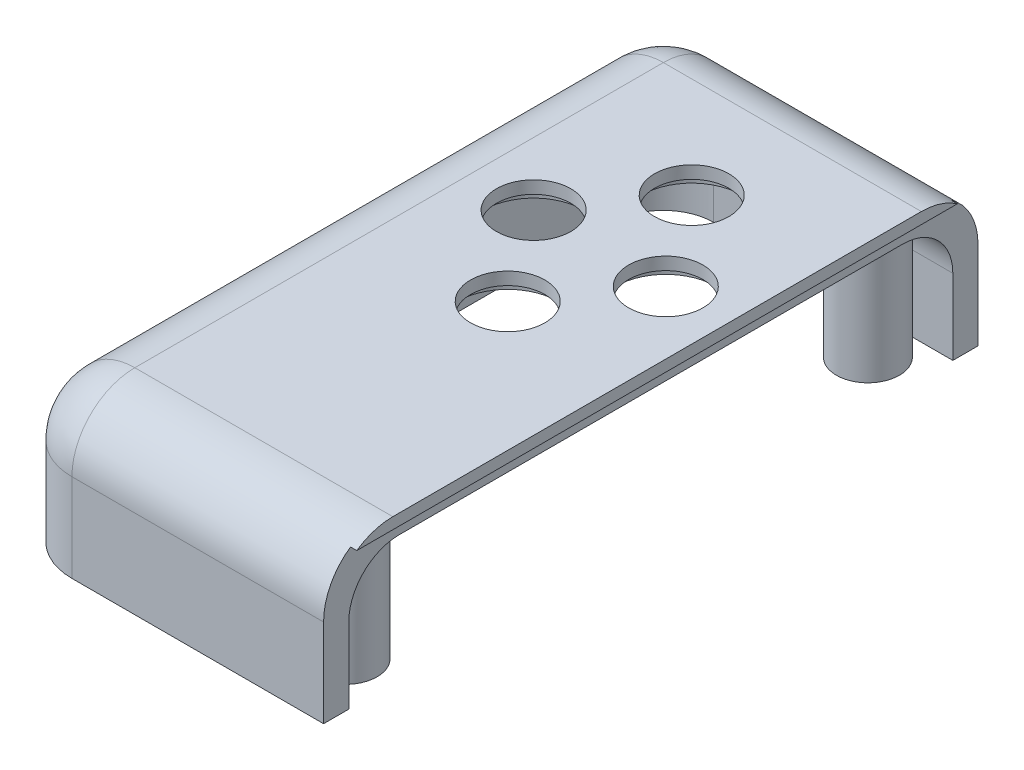
SolidWorks part; units mm, degrees
material "ABS"
ref_plane "Front Plane" through (0, 0, 0) normal (0, 0, 1) x (1, 0, 0)
ref_plane "Top Plane" through (0, 0, 0) normal (0, 1, 0) x (1, 0, 0)
ref_plane "Right Plane" through (0, 0, 0) normal (1, 0, 0) x (0, 0, -1)
sketch "Sketch1" plane through (0, 0, 0) normal (0, 1, 0) x (1, 0, 0)
  line L1 (0, 0) -> (63.5, 0)
  line L2 (0, 0) -> (0, 132.08)
  line L3 (0, 132.08) -> (63.5, 132.08)
  line L4 (63.5, 0) -> (63.5, 132.08)
  dimension "D1" = 132.08
  dimension "D2" = 63.5
extrude "Boss-Extrude1" add sketch "Sketch1" along normal blind 5.08
sketch "Sketch2" plane through (0, 0, 0) normal (0, -1, 0) x (1, 0, 0)
  line L0 (0, -132.08) -> (0, 0) construction
  line L1 (63.5, -132.08) -> (0, -132.08) construction
  circle A0 centre (54.356, -118.999) radius 6.35
  circle A1 centre (54.356, -118.999) radius 5.08
  circle A2 centre (54.356, -13.589) radius 6.35
  circle A3 centre (54.356, -13.589) radius 5.08
  dimension "D1" = 12.7
  dimension "D2" = 10.16
  dimension "D3" = 12.7
  dimension "D4" = 10.16
  dimension "D5" = 54.356
  dimension "D6" = 105.41
  dimension "D7" = 13.081
extrude "Boss-Extrude2" add sketch "Sketch2" along normal blind 25.4
sketch "Sketch3" plane through (0, 0, 0) normal (0, -1, 0) x (1, 0, 0)
  line L0 (63.5, -132.08) -> (0, -132.08)
  line L1 (0, -132.08) -> (0, 0)
  line L2 (0, 0) -> (63.5, 0)
  line L3 (63.5, 0) -> (63.5, -5.08)
  line L4 (63.5, 0) -> (63.5, -132.08) construction
  line L5 (63.5, -5.08) -> (5.08, -5.08)
  line L6 (5.08, -5.08) -> (5.08, -127)
  line L7 (5.08, -127) -> (63.5, -127)
  line L8 (63.5, -127) -> (63.5, -132.08)
  dimension "D1" = 5.08
  dimension "D2" = 5.08
  dimension "D3" = 5.08
extrude "Boss-Extrude3" add sketch "Sketch3" along normal blind 25.4
fillet "Fillet1" radius 12.7 2 edges at (31.75, 5.08, 0) (31.75, 5.08, -132.08)
sketch "Sketch4" plane through (63.5, 0, 0) normal (1, 0, 0) x (0, 0, -1)
  line L1 (5.431, 2.794) -> (126.649, 2.794)
  line L3 (12.7, 5.08) -> (119.38, 5.08)
  line L6 (12.7, 5.08) -> (119.38, 5.08) construction
  arc A0 (132.08, -7.62) -> (119.38, 5.08) centre (119.38, -7.62) ccw construction
  arc A1 (12.7, 5.08) -> (0, -7.62) centre (12.7, -7.62) ccw construction
  arc A2 (119.38, 5.08) -> (126.649, 2.794) centre (119.38, -7.62) cw
  arc A3 (12.7, 5.08) -> (5.431, 2.794) centre (12.7, -7.62) ccw
  dimension "D1" = 2.286
extrude "Boss-Extrude4" add sketch "Sketch4" along normal blind 1.27
sketch "Sketch7" plane through (0, 5.08, 0) normal (0, 1, 0) x (1, 0, 0)
  line L0 (0, 0) -> (0, 132.08) construction
  line L2 (0, 132.08) -> (63.5, 132.08) construction
  circle A0 centre (38.735, 99.06) radius 7.5
  circle A1 centre (25.4, 80.4924) radius 7.5
  circle A2 centre (52.07, 80.4924) radius 7.5
  circle A3 centre (38.735, 61.9247) radius 7.5
  dimension "D1" = 15
  dimension "D2" = 15
  dimension "D3" = 15
  dimension "D4" = 15
  dimension "D6" = 25.4
  dimension "D5" = 26.67
  dimension "D7" = 22.86
  dimension "D8" = 22.86
  dimension "D9" = 22.86
  dimension "D10" = 33.02
extrude "Cut-Extrude1" cut sketch "Sketch7" against normal through all
sketch "Sketch8" plane through (0, 0, 0) normal (0, -1, 0) x (1, 0, 0)
  circle A2 centre (38.735, -99.06) radius 10.16
  circle A3 centre (38.735, -99.06) radius 7.5
  circle A4 centre (25.4, -80.4924) radius 7.5
  circle A5 centre (25.4, -80.4924) radius 10.16
  circle A6 centre (52.07, -80.4924) radius 7.5
  circle A7 centre (52.07, -80.4924) radius 10.16
  circle A8 centre (38.735, -61.9247) radius 7.5
  circle A9 centre (38.735, -61.9247) radius 10.16
  circle A10 centre (52.07, -80.4924) radius 7.5 construction
  circle A11 centre (25.4, -80.4924) radius 7.5 construction
  circle A12 centre (38.735, -61.9247) radius 7.5 construction
  circle A13 centre (38.735, -99.06) radius 7.5 construction
  circle A14 centre (25.4, -80.4924) radius 7.5 construction
  circle A15 centre (52.07, -80.4924) radius 7.5 construction
  circle A16 centre (38.735, -61.9247) radius 7.5 construction
  dimension "D1" = 20.32
  dimension "D2" = 20.32
  dimension "D3" = 20.32
  dimension "D4" = 20.32
extrude "Cut-Extrude2" cut sketch "Sketch8" against normal blind 2.54
fillet "Fillet3" radius 10.16 5 edges at (5.08, -12.7, -127) (5.08, -12.7, -5.08) (34.29, 0, -5.08) (5.08, 0, -66.04) (34.29, 0, -127)
fillet "Fillet4" radius 12.7 5 edges at (0, -16.51, -132.08) (0, 1.3603, -128.3603) (0, -16.51, 0) (0, 1.3603, -3.7197) (0, 5.08, -66.04)
